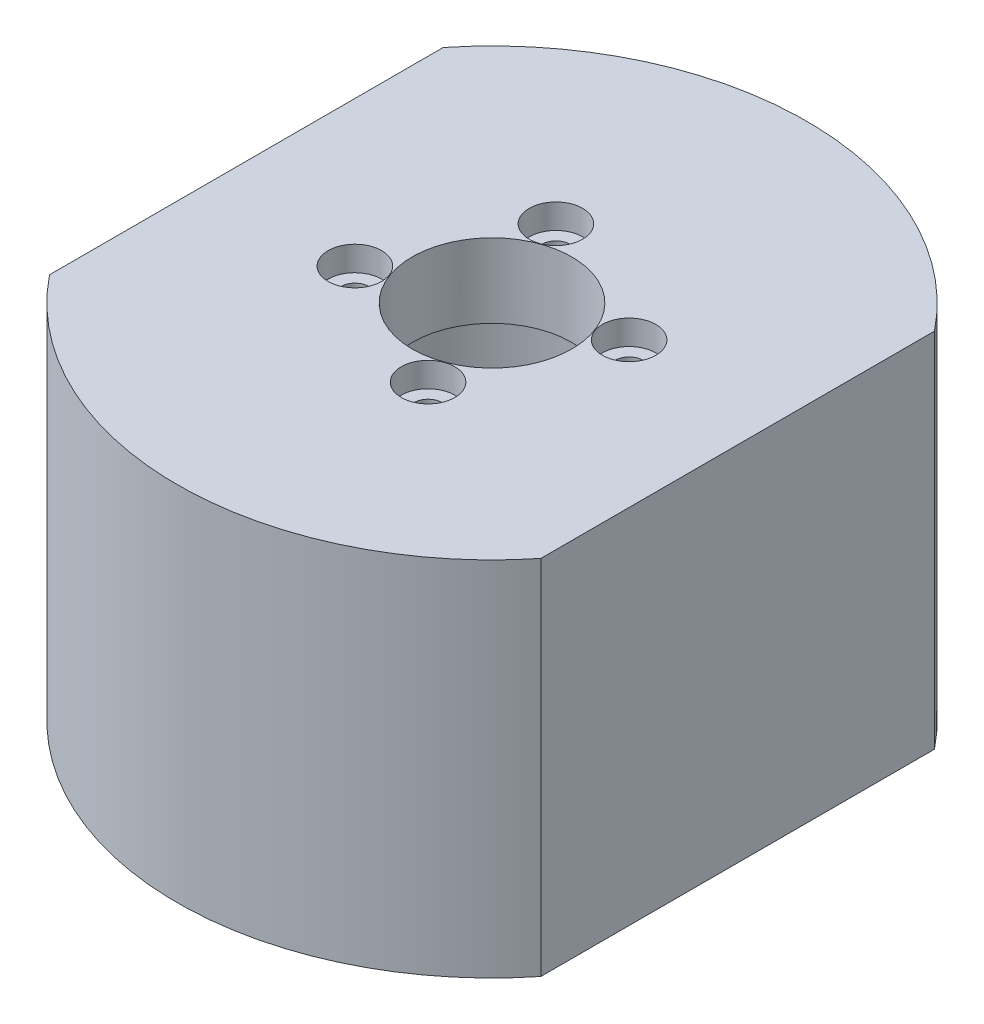
SolidWorks part; units mm, degrees
ref_plane "Front Plane" through (0, 0, 0) normal (0, 0, 1) x (1, 0, 0)
ref_plane "Top Plane" through (0, 0, 0) normal (0, 1, 0) x (1, 0, 0)
ref_plane "Right Plane" through (0, 0, 0) normal (1, 0, 0) x (0, 0, -1)
sketch "Sketch1" plane through (0, 0, 0) normal (0, 1, 0) x (1, 0, 0)
  line L0 (-29.85, 23.9174) -> (-29.85, -23.9174)
  line L1 (29.85, 23.9174) -> (29.85, -23.9174)
  line L2 (-29.85, 0) -> (29.85, 0) construction
  arc A0 (-29.85, -23.9174) -> (29.85, -23.9174) centre (0, 0) ccw
  arc A1 (29.85, 23.9174) -> (-29.85, 23.9174) centre (0, 0) ccw
  point P9 (0, 0)
  point P10 (-29.85, 25.5695)
  point P11 (0, 0)
  point P12 (0, 0)
  point P13 (0, 0)
  dimension "D1" = 59.7
  dimension "D2" = 76.5
extrude "Boss-Extrude1" add sketch "Sketch1" along normal blind 44
sketch "Sketch2" plane through (0, 44, 0) normal (0, 1, 0) x (1, 0, 0)
  line L0 (-4.4463, 12.216) -> (0, 0) construction
  line L1 (0, 13) -> (0, 0) construction
  circle A0 centre (0, 0) radius 13
  point P3 (-4.4463, 12.216)
  dimension "D1" = 26
  dimension "D2" = 20
hole_wizard "CBORE for M3 SHCS1" positions "Sketch2" profile "Sketch3" counterbore size "M3" standard "ANSI Metric" end condition through all
sketch "Sketch3" plane through (-4.4463, 44, -12.216) normal (1, 0, 0) x (0, 0, 1)
  line L0 (0, 0) -> (0, 44)
  line L1 (0, 44) -> (1.7, 44)
  line L3 (1.7, 44) -> (1.7, 3)
  line L4 (1.7, 3) -> (3.25, 3)
  line L5 (3.25, 3) -> (3.25, 0)
  line L7 (3.25, 0) -> (0, 0)
  line L11 (0, -6.35) -> (0, 107.95) construction
  dimension "Thru Hole Dia." = 3.4
  dimension "Thru Hole Depth" = 44
  dimension "C'Bore Dia." = 6.5
  dimension "C'Bore Depth" = 3
ref_axis "Axis1" through (0, 44, 0) along (0, -1, 0)
pattern_circular "CirPattern1" count 4 every 90 about axis through (0, 44, 0) along (0, -1, 0) of "CBORE for M3 SHCS1"
sketch "Sketch4" plane through (0, 0, 0) normal (0, -1, 0) x (1, 0, 0)
  circle A0 centre (0, 0) radius 16.2
  dimension "D1" = 32.4
extrude "Cut-Extrude1" cut sketch "Sketch4" against normal blind 35
sketch "Sketch5" plane through (0, 44, 0) normal (0, 1, 0) x (1, 0, 0)
  circle A0 centre (0, 0) radius 9.7
extrude "Cut-Extrude2" cut sketch "Sketch5" against normal through all
ref_plane "Plane1" through (0, 0, -38.25) normal (0, 0, -1) x (-1, 0, 0)
sketch "Sketch6" plane through (0, 0, -38.25) normal (0, 0, -1) x (-1, 0, 0)
  line L0 (-29.85, 44) -> (-29.85, 0) construction
  line L1 (-29.85, 0) -> (29.85, 0) construction
  circle A0 centre (-20.75, 6.85) radius 1.7
  dimension "D1" = 9.1
  dimension "D2" = 6.85
